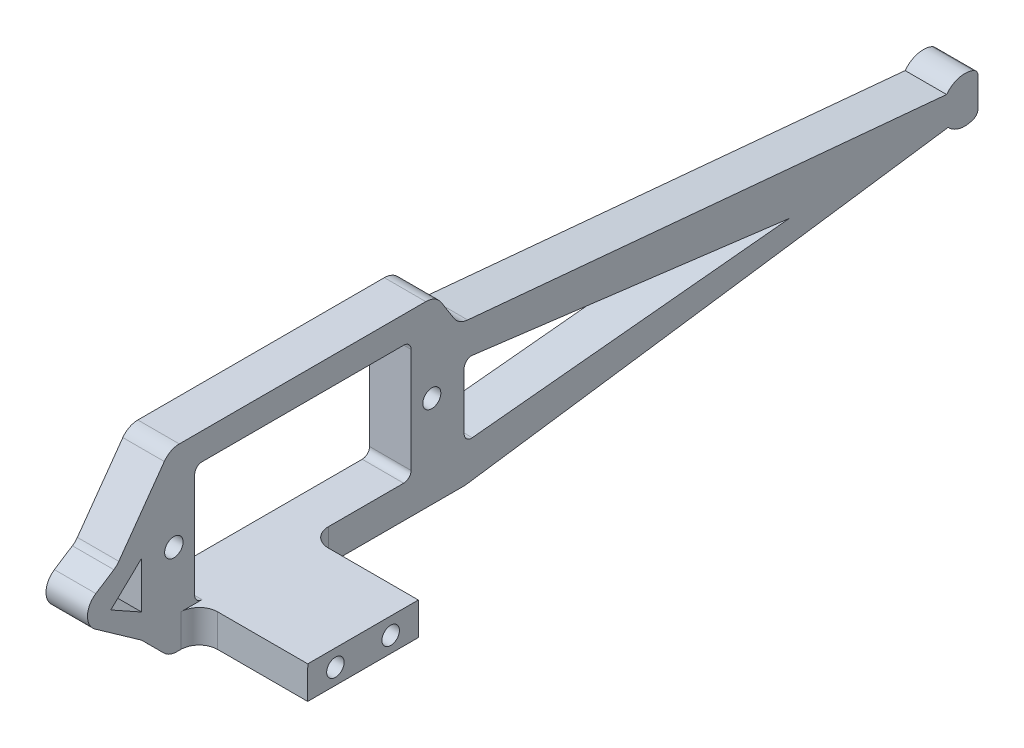
SolidWorks part; units mm, degrees
ref_plane "前视基准面" through (0, 0, 0) normal (0, 0, 1) x (1, 0, 0)
ref_plane "上视基准面" through (0, 0, 0) normal (0, 1, 0) x (1, 0, 0)
ref_plane "右视基准面" through (0, 0, 0) normal (1, 0, 0) x (0, 0, -1)
other "Configuration Table"
other "图形1"
other "图形 (打开) -1"
sketch "草图1" plane through (0, 0, 0) normal (1, 0, 0) x (0, 0, -1)
  line L0 (-39.3216, -59.7708) -> (-31.8802, -65.027)
  line L1 (-31.8802, -65.027) -> (-28.8835, -68.0265)
  line L2 (-28.8835, -68.0265) -> (3.216, -68.0265)
  line L3 (3.216, -68.0265) -> (55.6399, -60.5993)
  line L4 (-39.3216, -59.7708) -> (-34.5721, -56.6898)
  line L5 (-34.5721, -56.6898) -> (-28.8199, -48.6271)
  line L6 (-28.8199, -48.6271) -> (0.0642, -48.6271)
  line L7 (0.0642, -48.6271) -> (2.5196, -52.5319)
  line L8 (2.5196, -52.5319) -> (55.4741, -57.4238)
  line L9 (-26.1203, -51.5388) -> (-26.1203, -64.4934)
  line L10 (-26.1203, -64.4934) -> (-2.6415, -64.4934)
  line L11 (-2.6415, -64.4934) -> (-2.6304, -51.5271)
  line L12 (-2.6304, -51.5271) -> (-26.1203, -51.5388)
  line L13 (3.1196, -56.0869) -> (3.1196, -64.0244)
  line L14 (3.1196, -64.0244) -> (38.4037, -60.5335)
  line L15 (38.4037, -60.5335) -> (3.1196, -56.0869)
  line L16 (-31.8802, -57.3267) -> (-31.8804, -62.3796)
  line L17 (-31.8804, -62.3796) -> (-35.2237, -60.5151)
  line L18 (-35.2237, -60.5151) -> (-31.8802, -57.3267)
  line L19 (58.8803, -60.9315) -> (58.8803, -56.894)
  arc A0 (55.4741, -57.4238) -> (58.8803, -56.894) centre (57.45, -58.9128) cw
  circle A1 centre (-0.3894, -58.0375) radius 0.979
  circle A2 centre (-28.381, -58.0375) radius 1.0006
  arc A3 (58.8803, -60.9315) -> (55.6399, -60.5993) centre (57.45, -58.9128) cw
  point P35 (58.8803, -56.894)
extrude "凸台-拉伸1" add sketch "草图1" along normal blind 4.5
sketch "草图2" plane through (4.5, 0, 0) normal (1, 0, 0) x (0, 0, -1)
  line L1 (-25.6269, -68.0265) -> (-25.6206, -64.4934)
  line L3 (-13.6206, -64.4934) -> (-13.6206, -68.0265)
  line L4 (-19.6206, -64.5378) -> (-19.6206, -74.6463) construction
  line L5 (-26.1203, -64.4934) -> (-2.6415, -64.4934) construction
  line L6 (-25.6269, -68.0265) -> (-13.6206, -68.0265)
  line L7 (-28.8835, -68.0265) -> (3.216, -68.0265) construction
  line L8 (-13.6206, -64.4934) -> (-25.6206, -64.4934)
  circle A0 centre (-22.6206, -66.3174) radius 0.95
  circle A1 centre (-16.6206, -66.3174) radius 0.95
  dimension "D3" = 1.9
  dimension "D1" = 3
  dimension "D2" = 3
extrude "凸台-拉伸2" add sketch "草图2" along normal blind 11.7699
fillet "圆角1" radius 2 8 edges at (2.25, -68.0265, 28.8835) (2.25, -56.6898, 34.5721) (2.25, -59.7708, 39.3216) (2.25, -48.6271, 28.8199) (2.25, -48.6271, -0.0642) (2.25, -52.5319, -2.5196) (4.5, -66.26, 13.6206) (4.5, -66.26, 25.6237)
fillet "圆角2" radius 0.8 8 edges at (2.25, -64.4934, 26.1203) (2.25, -51.5388, 26.1203) (2.25, -51.5271, 2.6304) (2.25, -64.4934, 2.6415) (2.25, -56.0869, -3.1196) (2.25, -64.0244, -3.1196) (2.25, -60.9315, -58.8803) (2.25, -56.894, -58.8803)
